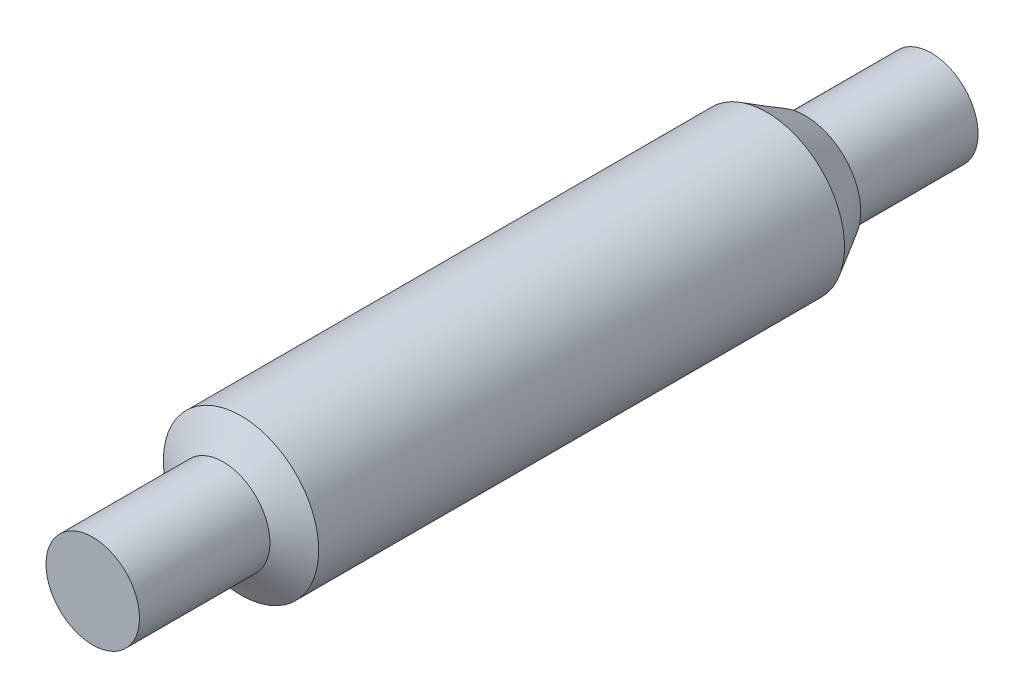
SolidWorks part; units mm, degrees
ref_plane "Front Plane" through (0, 0, 0) normal (0, 0, 1) x (1, 0, 0)
ref_plane "Top Plane" through (0, 0, 0) normal (0, 1, 0) x (1, 0, 0)
ref_plane "Right Plane" through (0, 0, 0) normal (1, 0, 0) x (0, 0, -1)
sketch "Sketch2" plane through (0, 0, 0) normal (0, 0, 1) x (1, 0, 0)
  circle A0 centre (0, 160.02) radius 5.35
  arc A1 (-6.35, 160.02) -> (6.35, 160.02) centre (0, 160.02) ccw construction
  dimension "D1" = 1
extrude "Boss-Extrude1" add sketch "Sketch2" along normal offset from surface 5.08 and the other way offset from surface (47.99 mm away) 5.08
sketch "Sketch3" plane through (0, 0, 0) normal (0, 0, 1) x (1, 0, 0)
  circle A0 centre (0, 160.02) radius 8.89
  dimension "D1" = 17.78
extrude "Boss-Extrude2" add sketch "Sketch3" along normal offset from surface 3 and the other way offset from surface (33.56 mm away) 3
chamfer "Chamfer1" distance 2.54 angle 60 2 edges at (-8.89, 160.02, -33.56) (8.89, 160.02, 33.56)
